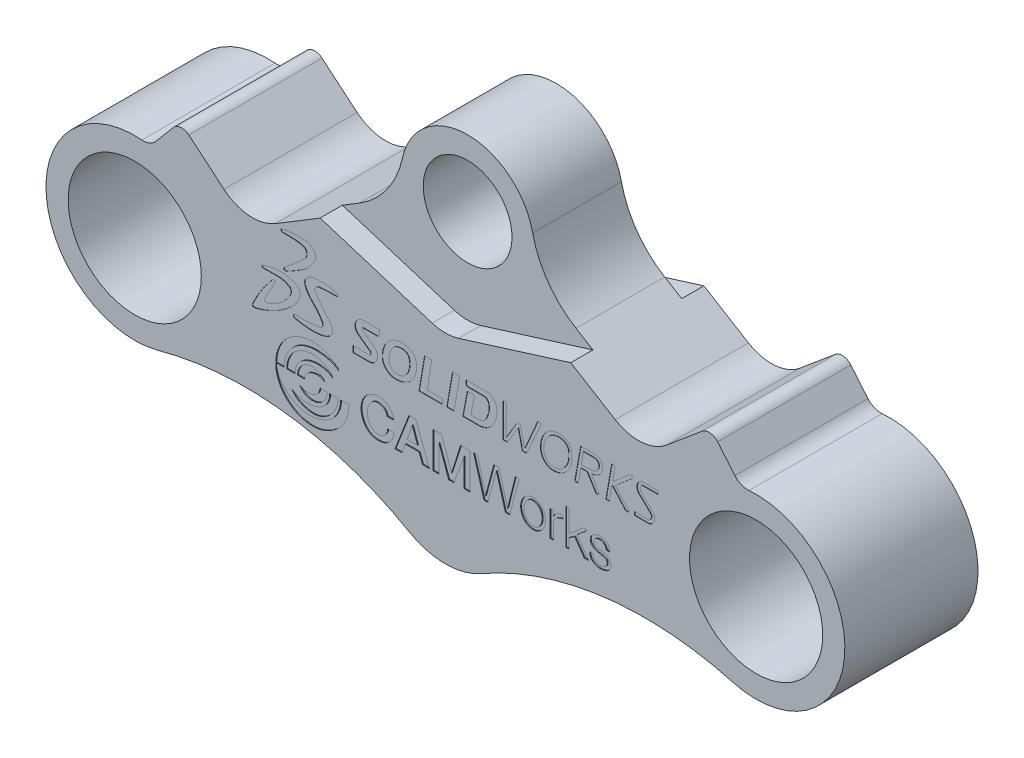
SolidWorks part; units mm, degrees
material "6061-T6 (SS)"
ref_plane "Front Plane" through (0, 0, 0) normal (0, 0, 1) x (1, 0, 0)
ref_plane "Top Plane" through (0, 0, 0) normal (0, 1, 0) x (1, 0, 0)
ref_plane "Right Plane" through (0, 0, 0) normal (1, 0, 0) x (0, 0, -1)
sketch "Sketch1" plane through (0, 0, 0) normal (0, 0, 1) x (1, 0, 0)
  line L0 (0, 0) -> (44.45, 7.8377) construction
  line L1 (0, 0) -> (0, 31.75) construction
  line L2 (0, 0) -> (0, -25.1431) construction
  line L3 (0, 0) -> (113.4618, 0) construction
  line L4 (44.45, 7.8377) -> (33.8059, 20.5229) construction
  line L5 (44.45, 7.8377) -> (44.45, 35.5738) construction
  line L11 (37.9229, 25.4953) -> (41.4081, 21.3418)
  line L13 (37.9229, 25.4953) -> (28.1941, 17.3319)
  line L14 (-44.45, 7.8377) -> (-33.8059, 20.5229) construction
  line L17 (28.1941, 17.3319) -> (15.505, 25.046)
  line L18 (0, 0) -> (-44.45, 7.8377) construction
  line L19 (-28.1941, 17.3319) -> (-15.505, 25.046)
  line L22 (-37.9229, 25.4953) -> (-28.1941, 17.3319)
  line L24 (-37.9229, 25.4953) -> (-41.4081, 21.3418)
  circle A0 centre (0, 31.75) radius 7.9375 construction
  circle A2 centre (0, 0) radius 5.5562 construction
  circle A3 centre (44.45, 7.8377) radius 9.525 construction
  arc A5 (41.4081, 21.3418) -> (43.429, 20.4966) centre (43.2371, 22.8765) ccw
  circle A7 centre (0, 31.75) radius 9.525 construction
  arc A8 (10.3187, 0) -> (10.162, 1.7918) centre (0, 0) ccw
  arc A9 (5.1295, -8.9535) -> (41.0791, -4.4067) centre (28.5656, -49.8611) cw
  arc A10 (9.3119, 33.7533) -> (-9.3119, 33.7533) centre (0, 31.75) ccw
  arc A11 (15.505, 25.046) -> (9.3119, 33.7533) centre (22.5268, 36.5963) cw
  arc A12 (41.0791, -4.4067) -> (43.429, 20.4966) centre (44.45, 7.8377) ccw
  circle A13 centre (0, 0) radius 10.3187 construction
  arc A14 (-41.0791, -4.4067) -> (-43.429, 20.4966) centre (-44.45, 7.8377) cw
  arc A15 (-15.505, 25.046) -> (-9.3119, 33.7533) centre (-22.5268, 36.5963) ccw
  arc A16 (-5.1295, -8.9535) -> (-41.0791, -4.4067) centre (-28.5656, -49.8611) ccw
  arc A19 (-41.4081, 21.3418) -> (-43.429, 20.4966) centre (-43.2371, 22.8765) cw
  circle A21 centre (-44.45, 7.8377) radius 9.525 construction
  arc A22 (-5.1295, -8.9535) -> (5.1295, -8.9535) centre (0, 0) ccw
  point P26 (9.1088, 28.1848)
  point P35 (9.8679, 3.0169)
  dimension "D1" = 15.875
  dimension "D3" = 11.1125
  dimension "D6" = 19.05
  dimension "D12" = 2.3876
  dimension "D4" = 44.45
  dimension "D5" = 31.75
  dimension "D7" = 10
  dimension "D8" = 40
  dimension "D16" = 4.7625
  dimension "D17" = 1.5875
extrude "Boss-Extrude1" add sketch "Sketch1" along normal mid plane 19.05 contours A16 A22 A9 A12 A5 L11 A3 L13 L17 A11 A10 A15 L19 L22 A21 L24 A19 A14 A0 A2 region at (0, 10.8738, 0)
fillet "Fillet19" radius 6.35 2 edges at (28.1941, 17.3319, 0) (-28.1941, 17.3319, 0)
fillet "Fillet20" radius 1.5875 2 edges at (37.9229, 25.4953, 0) (-37.9229, 25.4953, 0)
sketch "Sketch2" plane through (0, 0, 9.525) normal (0, 0, 1) x (1, 0, 0)
  line L0 (11.5116, 28.7617) -> (22.65, -3.0883)
  line L1 (22.65, -3.0883) -> (47.5098, -15.7051)
  line L2 (47.5098, -15.7051) -> (71.0787, 26.7896)
  line L3 (71.0787, 26.7896) -> (23.8861, 37.9468)
  line L4 (23.8861, 37.9468) -> (11.5116, 28.7617)
  arc A0 (9.3119, 33.7533) -> (15.505, 25.046) centre (22.5268, 36.5963) ccw construction
  arc A1 (41.0791, -4.4067) -> (5.1295, -8.9535) centre (28.5656, -49.8611) ccw construction
sketch "Sketch3" plane through (0, 0, 9.525) normal (0, 0, 1) x (1, 0, 0)
  line L0 (0, 0) -> (0, 51.1761) construction
  line L1 (-13.039, 44.2465) -> (13.039, 44.2465)
  line L2 (13.039, 44.2465) -> (19.3473, 24.0178)
  line L3 (19.3473, 24.0178) -> (0, 17.9843)
  line L4 (-19.3473, 24.0178) -> (0, 17.9843)
  line L5 (-13.039, 44.2465) -> (-19.3473, 24.0178)
  point P9 (0, 44.2465)
extrude "Cut-Extrude2" cut sketch "Sketch3" against normal blind 3.175
fillet "Fillet9" radius 6.35 1 edges at (0, 17.9843, 7.9375)
mirror "Mirror13" about plane through (0, 0, 0) normal (0, 0, 1) of "Cut-Extrude2"
fillet "Fillet14" radius 6.35 1 edges at (0, 17.9843, -7.9375)
hole_wizard "1/2 (0.5) Diameter Hole1" positions "Sketch11" profile "Sketch12" hole size "1/2" standard "ANSI Inch" end condition through all
sketch "Sketch11" plane through (0, 0, 6.35) normal (0, 0, 1) x (1, 0, 0)
  point P0 (0, 31.75)
sketch "Sketch12" plane through (0, 31.75, 6.35) normal (1, 0, 0) x (0, -1, 0)
  line L0 (0, 0) -> (0, 15.875)
  line L1 (0, 15.875) -> (6.35, 15.875)
  line L2 (6.35, 15.875) -> (6.35, 0)
  line L5 (6.35, 0) -> (0, 0)
  line L11 (0, -6.35) -> (0, 107.95) construction
  dimension "Thru Hole Dia." = 12.7
  dimension "Thru Hole Depth" = 15.875
hole_wizard "3/4 (0.75) Diameter Hole1" positions "Sketch13" profile "Sketch14" hole size "3/4" standard "ANSI Inch" end condition through all
sketch "Sketch13" plane through (0, 0, 9.525) normal (0, 0, 1) x (1, 0, 0)
  point P0 (-44.45, 7.8377)
  point P3 (44.45, 7.8377)
sketch "Sketch14" plane through (-44.45, 7.8377, 9.525) normal (1, 0, 0) x (0, -1, 0)
  line L0 (0, 0) -> (0, 19.05)
  line L1 (0, 19.05) -> (9.525, 19.05)
  line L2 (9.525, 19.05) -> (9.525, 0)
  line L5 (9.525, 0) -> (0, 0)
  line L11 (0, -6.35) -> (0, 107.95) construction
  dimension "Thru Hole Dia." = 19.05
  dimension "Thru Hole Depth" = 19.05
sketch "Sketch19" plane through (0, 0, 9.525) normal (0, 0, 1) x (1, 0, 0)
  line L0 (0, 0) -> (0, 52.7084) construction
  circle A0 centre (44.45, 7.8377) radius 11.1125
  circle A1 centre (-44.45, 7.8377) radius 11.1125
  dimension "D1" = 22.225
sketch "Sketch20" plane through (0, 0, 9.525) normal (0, 0, 1) x (1, 0, 0)
  line L0 (-24.2613, 2.5064) -> (-23.1024, 2.5064)
  line L1 (-21.1371, 2.5064) -> (-20.1303, 2.5064)
  line L2 (-22.6988, 2.5064) -> (-21.5016, 2.5064)
  line L3 (-16.9282, 2.5064) -> (-17.96, 2.5064)
  line L4 (-15.4082, 2.5064) -> (-16.5618, 2.5064)
  line L5 (16.8161, 3.6153) -> (16.8161, 4.1275)
  line L6 (15.4419, 0.3486) -> (15.4419, 2.6934)
  line L7 (14.9756, 0.3486) -> (15.4419, 0.3486)
  line L8 (14.9756, 4.0314) -> (14.9756, 0.3486)
  line L9 (15.4419, 4.0314) -> (14.9756, 4.0314)
  line L10 (15.4419, 3.3134) -> (15.4419, 4.0314)
  line L11 (23.0367, 2.9061) -> (23.4912, 2.9061)
  line L12 (21.1196, 1.5282) -> (20.6711, 1.5282)
  line L24 (-8.3465, 3.7921) -> (-7.4097, 3.7921)
  line L25 (-7.3744, 2.2787) -> (-8.2537, 2.2787)
  line L26 (2.6811, 4.3434) -> (2.6811, 0.3486)
  line L27 (2.6811, 0.3486) -> (3.4934, 0.3486)
  line L28 (3.4934, 0.3486) -> (3.4934, 5.4578)
  line L29 (3.4934, 5.4578) -> (2.1789, 5.4578)
  line L30 (2.1789, 5.4578) -> (0.8894, 1.4078)
  line L31 (0.8894, 1.4078) -> (-0.5714, 5.461)
  line L32 (-0.5714, 5.461) -> (-1.7638, 5.461)
  line L33 (-1.7638, 5.461) -> (-1.7638, 0.3486)
  line L34 (-1.7638, 0.3486) -> (-0.9199, 0.3486)
  line L35 (-0.9199, 0.3486) -> (-0.9199, 4.2121)
  line L36 (-0.9199, 4.2121) -> (0.4726, 0.3486)
  line L37 (0.4726, 0.3486) -> (1.2108, 0.3486)
  line L38 (1.2108, 0.3486) -> (2.6811, 4.3434)
  line L39 (-4.7419, 4.5102) -> (-5.4681, 2.3913)
  line L40 (-3.9888, 2.3913) -> (-4.7419, 4.5102)
  line L41 (-5.4681, 2.3913) -> (-3.9888, 2.3913)
  line L42 (-24.2066, 2.489) -> (-24.2618, 2.489)
  line L43 (-13.8028, 2.5064) -> (-14.9977, 2.5064)
  line L44 (-5.7285, 1.6607) -> (-3.7553, 1.6607)
  line L45 (-6.2391, 0.3486) -> (-5.7285, 1.6607)
  line L46 (-7.2018, 0.3486) -> (-6.2391, 0.3486)
  line L47 (-5.212, 5.461) -> (-7.2018, 0.3486)
  line L48 (-4.2247, 5.461) -> (-5.212, 5.461)
  line L49 (-2.2957, 0.3486) -> (-4.2247, 5.461)
  line L50 (-3.2602, 0.3486) -> (-2.2957, 0.3486)
  line L51 (-3.7553, 1.6607) -> (-3.2602, 0.3486)
  line L52 (17.2152, 0.3486) -> (17.6916, 0.3486)
  line L53 (17.6916, 0.3486) -> (17.6916, 1.7618)
  line L54 (17.6916, 1.7618) -> (18.4695, 2.3165)
  line L55 (18.4695, 2.3165) -> (19.8729, 0.3486)
  line L56 (19.8729, 0.3486) -> (20.4853, 0.3486)
  line L57 (20.4853, 0.3486) -> (18.8132, 2.6934)
  line L58 (18.8132, 2.6934) -> (20.3356, 4.0074)
  line L59 (20.3356, 4.0074) -> (19.7018, 4.0074)
  line L60 (19.7018, 4.0074) -> (17.6916, 2.2723)
  line L61 (17.6916, 2.2723) -> (17.6916, 5.461)
  line L62 (17.6916, 5.461) -> (17.2152, 5.461)
  line L63 (17.2152, 5.461) -> (17.2152, 0.3486)
  line L64 (4.0328, 5.4578) -> (5.522, 0.3486)
  line L65 (5.522, 0.3486) -> (6.0506, 0.3486)
  line L66 (6.0506, 0.3486) -> (7.2887, 4.8318)
  line L67 (7.2887, 4.8318) -> (8.5954, 0.3486)
  line L68 (8.5954, 0.3486) -> (9.1816, 0.3486)
  line L69 (9.1816, 0.3486) -> (10.5463, 5.461)
  line L70 (10.5463, 5.461) -> (10.0007, 5.461)
  line L71 (10.0007, 5.461) -> (8.8885, 0.9778)
  line L72 (8.8885, 0.9778) -> (7.6674, 5.461)
  line L73 (7.6674, 5.461) -> (6.934, 5.461)
  line L74 (6.934, 5.461) -> (5.7373, 0.9778)
  line L75 (5.7373, 0.9778) -> (4.6136, 5.4578)
  line L76 (4.6136, 5.4578) -> (4.0328, 5.4578)
  ellipse E0 centre (12.5441, 2.204) end of major axis (12.4598, 0.1977) minor radius 1.779
  ellipse E1 centre (12.5441, 2.204) end of major axis (12.5441, 3.7921) minor radius 1.3127
  spline S0 degree 3 poles (-23.1024, 2.5064) (-23.0971, 3.5859) (-22.4651, 5.2251) (-20.5491, 6.6301) (-18.078, 7.1112) (-16.1966, 6.6039) (-15.1548, 5.9628) knots 0 0 0 0 0.304367 0.466255 0.655371 1 1 1 1
  spline S1 degree 3 poles (-15.1548, 5.9628) (-15.5783, 6.5498) (-16.8375, 7.4484) (-18.9616, 7.893) (-21.0692, 7.4482) (-23.4121, 5.9658) (-24.2655, 3.8586) (-24.2613, 2.5064) knots 0 0 0 0 0.172137 0.357725 0.501203 0.677746 1 1 1 1
  spline S2 degree 3 poles (-20.1303, 2.5064) (-20.1324, 2.9593) (-19.6326, 3.6975) (-18.3871, 4.0366) (-17.5768, 3.8704) (-17.2458, 3.5736) knots 0 0 0 0 0.355167 0.653312 1 1 1 1
  spline S3 degree 3 poles (-17.2458, 3.5736) (-17.4055, 3.9058) (-17.9769, 4.444) (-19.1021, 4.7031) (-20.5335, 4.2616) (-21.1665, 3.2292) (-21.1371, 2.5064) knots 0 0 0 0 0.202687 0.415279 0.607942 1 1 1 1
  spline S4 degree 3 poles (-21.5016, 2.5064) (-21.5879, 3.3398) (-20.8524, 4.5882) (-19.1216, 5.3) (-17.5419, 5.3116) (-16.5539, 4.9658) (-16.1028, 4.6737) knots 0 0 0 0 0.336822 0.562344 0.770945 1 1 1 1
  spline S5 degree 3 poles (-16.1028, 4.6737) (-16.6594, 5.4446) (-18.0791, 6.3254) (-20.166, 6.0885) (-22.0368, 5.0527) (-22.7154, 3.5249) (-22.6988, 2.5064) knots 0 0 0 0 0.313136 0.502366 0.666444 1 1 1 1
  spline S6 degree 3 poles (-17.96, 2.5064) (-17.932, 1.8223) (-19.0083, 0.9185) (-20.3256, 1.0433) (-20.8296, 1.4355) knots 0 0 0 0 0.499578 1 1 1 1
  spline S7 degree 3 poles (-20.8296, 1.4355) (-20.5724, 0.9811) (-19.817, 0.3947) (-18.5061, 0.3779) (-17.3016, 1.0011) (-16.9361, 1.9615) (-16.9282, 2.5064) knots 0 0 0 0 0.287736 0.487574 0.695315 1 1 1 1
  spline S8 degree 3 poles (-16.5618, 2.5064) (-16.5115, 1.8371) (-16.9702, 0.6799) (-18.4014, -0.1179) (-20.0813, -0.4016) (-21.3098, -0.08) (-21.9604, 0.3429) knots 0 0 0 0 0.283056 0.482539 0.671248 1 1 1 1
  spline S9 degree 3 poles (-21.9604, 0.3429) (-21.5349, -0.3362) (-20.3963, -1.0126) (-18.5359, -1.271) (-16.9531, -0.6568) (-15.733, 0.6766) (-15.316, 1.8629) (-15.4082, 2.5064) knots 0 0 0 0 0.257455 0.416875 0.60526 0.789878 1 1 1 1
  spline S10 degree 3 poles (15.4419, 2.6934) (15.602, 2.9028) (15.8927, 3.463) (16.5054, 3.6094) (16.8161, 3.6153) knots 0 0 0 0 0.469307 1 1 1 1
  spline S11 degree 3 poles (16.8161, 4.1275) (16.2755, 4.1602) (15.6912, 3.8377) (15.4419, 3.3134) knots 0 0 0 0 1 1 1 1
  spline S12 degree 3 poles (23.4912, 2.9061) (23.5069, 3.3021) (23.4377, 3.5745) (22.8174, 4.1301) (22.0633, 4.2006) (21.4391, 4.1124) (20.7962, 3.6676) (20.6048, 2.8681) (21.4202, 2.0292) (22.2991, 2.0194) (23.1045, 1.7199) (23.2793, 1.0222) (22.5578, 0.5504) (21.6195, 0.5811) (21.0009, 1.1205) (21.1196, 1.5282) knots 0 0 0 0 0.067062 0.148975 0.20304 0.28682 0.328691 0.4252 0.488568 0.640215 0.674333 0.728187 0.813903 0.886703 1 1 1 1
  spline S13 degree 3 poles (20.6711, 1.5282) (20.614, 1.2217) (20.7979, 0.6477) (21.6707, 0.1651) (22.6282, 0.1318) (23.6557, 0.6248) (23.8047, 1.6699) (23.0039, 2.4509) (22.1415, 2.4551) (21.281, 2.7015) (21.2066, 3.5303) (21.8459, 3.7244) (22.6106, 3.789) (23.0273, 3.129) (23.0367, 2.9061) knots 0 0 0 0 0.091071 0.156874 0.280395 0.364886 0.466496 0.536468 0.665479 0.716573 0.778128 0.84612 0.890812 1 1 1 1
  spline S14 degree 3 poles (-7.4097, 3.7921) (-7.4612, 4.6654) (-8.603, 5.7637) (-10.3346, 5.5952) (-11.6171, 4.8127) (-12.1965, 3.3447) (-11.9341, 1.6356) (-11.0709, 0.4637) (-9.6771, 0.0852) (-8.2935, 0.3052) (-7.4939, 1.3895) (-7.3516, 2.0564) (-7.3744, 2.2787) knots 0 0 0 0 0.175331 0.271237 0.33858 0.47311 0.570736 0.688741 0.747217 0.858562 0.957457 1 1 1 1
  spline S15 degree 3 poles (-8.2537, 2.2787) (-8.2617, 1.7264) (-8.8948, 0.8033) (-10.1462, 0.9543) (-10.8222, 1.5142) (-11.2318, 2.5289) (-11.1606, 3.8265) (-10.1272, 4.9836) (-8.7838, 4.7625) (-8.3631, 4.0824) (-8.3465, 3.7921) knots 0 0 0 0 0.179682 0.286073 0.363963 0.452172 0.627882 0.757863 0.910918 1 1 1 1
  spline S16 degree 3 poles (-14.9977, 2.5064) (-14.9865, 1.5454) (-15.7297, -0.601) (-18.5104, -1.765) (-21.465, -1.4226) (-23.6002, 0.1837) (-24.1678, 1.9265) (-24.2066, 2.489) knots 0.001261 0.001261 0.001261 0.001261 0.216474 0.470316 0.597834 0.876936 1 1 1 1
  spline S17 degree 3 poles (-24.2618, 2.489) (-24.2696, 2.2031) (-24.2186, 1.4078) (-23.8399, 0.2067) (-22.8245, -1.2742) (-20.9046, -2.6451) (-18.1716, -2.9286) (-16.0515, -1.8894) (-14.3277, -0.2242) (-13.7779, 1.416) (-13.8028, 2.5064) knots 0 0 0 0 0.052567 0.145511 0.227179 0.378978 0.564372 0.699238 0.800017 0.99894 0.99894 0.99894 0.99894
extrude "Cut-Extrude7" cut sketch "Sketch20" against normal blind 0.127 contours L42 S17 L43 S16 | S8 S9 L4 | S6 S7 L3 | S2 S3 L1 | S4 S5 L2 | S0 S1 L0 | L25 S15 L24 S14 | L44 L51 L50 L49 L48 L47 L46 L45 L41 L39 L40 | L75 L76 L64 L65 L66 L67 L68 L69 L70 L71 L72 L73 L74 | E0 E1 | L5 S11 L10 L9 L8 L7 L6 S10 | L62 L63 L52 L53 L54 L55 L56 L57 L58 L59 L60 L61 | L12 S13 L11 S12 | L35 L36 L37 L38 L26 L27 L28 L29 L30 L31 L32 L33 L34 region at (-20.848, 7.292, 9.525) region at (-19.6828, 3.707, 9.525) region at (-20.3183, 4.7343, 9.525) region at (-18.3829, 1.3043, 9.525) region at (-17.9104, -0.9069, 9.525) region at (15.9644, 3.4053, 9.525) region at (22.1946, 2.1781, 9.525) region at (-11.2259, 2.7056, 9.525) region at (-19.4824, -1.7214, 9.525) region at (-6.0498, 1.0303, 9.525) region at (18.3267, 2.5398, 9.525) region at (4.3232, 5.375, 9.525) region at (12.6262, 4.1567, 9.525)
sketch "Sketch22" plane through (0, 0, 9.525) normal (0, 0, 1) x (1, 0, 0)
  line L0 (128.642, -102.015) -> (744.642, -102.015) construction
  line L1 (-2.9817, 13.981) -> (-3.772, 9.2249)
  line L2 (-3.772, 9.2249) -> (-0.4945, 9.2249)
  line L3 (-0.4945, 9.2249) -> (-0.3768, 9.9328)
  line L4 (-0.3768, 9.9328) -> (-2.6267, 9.9328)
  line L5 (-2.6267, 9.9328) -> (-1.954, 13.981)
  line L6 (-1.954, 13.981) -> (-2.9817, 13.981)
  line L7 (1.0211, 13.981) -> (2.0499, 13.981)
  line L8 (2.0499, 13.981) -> (1.2305, 9.2249)
  line L9 (1.2305, 9.2249) -> (0.2017, 9.2249)
  line L10 (0.2017, 9.2249) -> (1.0211, 13.981)
  line L11 (3.1314, 12.6346) -> (4.1476, 12.6346)
  line L12 (4.1476, 12.6346) -> (3.6475, 9.9687)
  line L13 (3.6475, 9.9687) -> (4.831, 9.9687)
  line L14 (-9.4112, 13.981) -> (-11.7339, 13.981)
  line L15 (-13.1933, 10.13) -> (-10.9089, 10.13)
  line L16 (-13.1933, 10.13) -> (-13.1933, 9.2599)
  line L17 (-13.1933, 9.2599) -> (-10.9525, 9.2599)
  line L18 (-12.4337, 11.8297) -> (-10.788, 10.6322)
  line L19 (-10.2413, 11.5241) -> (-11.8393, 12.6869)
  line L20 (-11.7836, 13.0429) -> (-9.652, 13.0429)
  line L21 (-9.652, 13.0429) -> (-9.4112, 13.3557)
  line L22 (-9.4112, 13.3557) -> (-9.4112, 13.981)
  line L23 (3.1314, 12.6346) -> (2.4906, 9.2182)
  line L24 (2.4906, 9.2182) -> (4.7833, 9.2182)
  line L25 (5.7029, 13.981) -> (2.9784, 13.981)
  line L26 (3.2614, 13.2046) -> (5.5148, 13.2046)
  line L27 (8.2456, 13.981) -> (8.2456, 9.1881)
  line L28 (8.2456, 9.1881) -> (8.8753, 9.1881)
  line L29 (8.8753, 9.1881) -> (10.4222, 11.7688)
  line L30 (10.4222, 11.7688) -> (10.9975, 9.1881)
  line L31 (10.9975, 9.1881) -> (11.6038, 9.1881)
  line L32 (11.6038, 9.1881) -> (13.7013, 13.7935)
  line L33 (13.7013, 13.7935) -> (13.6595, 13.981)
  line L34 (13.6595, 13.981) -> (13.2328, 13.981)
  line L35 (13.2328, 13.981) -> (11.3894, 9.7227)
  line L36 (11.3894, 9.7227) -> (11.3007, 9.7227)
  line L37 (11.3007, 9.7227) -> (10.7305, 12.2808)
  line L38 (10.7305, 12.2808) -> (10.245, 12.2808)
  line L39 (10.245, 12.2808) -> (8.7639, 9.81)
  line L40 (8.7639, 9.81) -> (8.6704, 9.81)
  line L41 (8.6704, 9.81) -> (8.7172, 13.981)
  line L42 (8.7172, 13.981) -> (8.2456, 13.981)
  line L43 (19.3559, 13.9497) -> (18.4979, 9.1881)
  line L44 (18.4979, 9.1881) -> (19.0009, 9.1881)
  line L45 (19.0009, 9.1881) -> (19.3711, 11.2425)
  line L46 (19.3711, 11.2425) -> (20.2877, 11.2425)
  line L47 (20.2877, 11.2425) -> (21.5443, 9.1881)
  line L48 (21.5443, 9.1881) -> (21.8765, 9.1881)
  line L49 (21.8765, 9.1881) -> (21.9714, 9.2599)
  line L50 (21.9714, 9.2599) -> (21.9714, 9.4455)
  line L51 (21.9714, 9.4455) -> (20.9322, 11.1444)
  line L52 (19.3559, 13.9497) -> (21.493, 13.9497)
  line L53 (20.9322, 11.2816) -> (20.9322, 11.1444)
  line L54 (19.7193, 13.4693) -> (19.455, 11.7225)
  line L55 (19.455, 11.7225) -> (20.3274, 11.7225)
  line L56 (19.7193, 13.4693) -> (21.3007, 13.4693)
  line L57 (23.7899, 13.9497) -> (22.9678, 9.1881)
  line L58 (22.9678, 9.1881) -> (23.4569, 9.1881)
  line L59 (23.4569, 9.1881) -> (23.8184, 11.2816)
  line L60 (23.8184, 11.2816) -> (23.946, 11.2816)
  line L61 (23.946, 11.2816) -> (25.767, 9.1881)
  line L62 (25.767, 9.1881) -> (26.1625, 9.1881)
  line L63 (26.1625, 9.1881) -> (26.2605, 9.3813)
  line L64 (26.2605, 9.3813) -> (24.2974, 11.5266)
  line L65 (24.2974, 11.5266) -> (26.8031, 13.7009)
  line L66 (26.8031, 13.7009) -> (26.8031, 13.9497)
  line L67 (26.8031, 13.9497) -> (26.3865, 13.9497)
  line L68 (26.3865, 13.9497) -> (23.946, 11.832)
  line L69 (23.946, 11.832) -> (24.2344, 13.8253)
  line L70 (24.2344, 13.8253) -> (24.1265, 13.9497)
  line L71 (24.1265, 13.9497) -> (23.7899, 13.9497)
  line L72 (30.4315, 13.9497) -> (28.1771, 13.9497)
  line L73 (27.7505, 12.1488) -> (29.2938, 10.682)
  line L74 (28.9432, 9.6786) -> (27.0483, 9.6964)
  line L75 (30.4315, 13.4925) -> (28.1771, 13.4925)
  line L76 (28.0655, 12.4802) -> (29.6088, 11.0134)
  line L77 (28.9388, 9.2214) -> (27.044, 9.2392)
  line L78 (30.4315, 13.9497) -> (30.4315, 13.4925)
  line L79 (27.0483, 9.6964) -> (27.044, 9.2392)
  line L80 (-23.039, 14.9078) -> (-21.8627, 15.8733)
  line L81 (2.9784, 13.3941) -> (2.9784, 13.981)
  arc A0 (-11.8393, 12.6869) -> (-11.7836, 13.0429) centre (-11.7201, 12.8506) cw
  arc A1 (-11.7339, 13.981) -> (-12.4337, 11.8297) centre (-11.7339, 12.7915) ccw
  arc A2 (-10.788, 10.6322) -> (-10.9089, 10.13) centre (-10.9525, 10.4061) cw
  arc A3 (-10.9525, 9.2599) -> (-10.2413, 11.5241) centre (-10.9525, 10.5037) ccw
  arc A4 (4.7833, 9.2182) -> (6.7117, 10.2158) centre (4.7833, 11.5808) ccw
  arc A5 (6.7117, 10.2158) -> (7.3259, 11.5671) centre (3.4936, 12.4937) ccw
  arc A6 (7.3259, 11.5671) -> (7.1901, 13.1196) centre (4.9502, 12.1415) ccw
  arc A7 (7.1901, 13.1196) -> (6.3859, 13.8651) centre (5.9338, 12.571) ccw
  arc A8 (6.3859, 13.8651) -> (5.7029, 13.981) centre (5.7029, 11.9102) ccw
  arc A9 (5.5148, 13.2046) -> (6.1315, 12.7825) centre (5.5148, 12.5431) cw
  arc A10 (6.1315, 12.7825) -> (6.2047, 11.6047) centre (4.3188, 12.0787) cw
  arc A11 (6.2047, 11.6047) -> (5.8719, 10.6917) centre (1.6368, 12.7527) cw
  arc A12 (4.831, 9.9687) -> (5.8719, 10.6917) centre (4.831, 11.0795) ccw
  arc A13 (-24.7542, 12.5152) -> (-27.6149, 8.0822) centre (-11.0495, 0.5318) ccw
  arc A14 (-27.6149, 8.0822) -> (-27.3909, 7.7836) centre (-27.4214, 7.994) ccw
  arc A15 (-27.3909, 7.7836) -> (-26.4475, 7.994) centre (-28.3136, 14.1415) ccw
  arc A16 (-26.4475, 7.994) -> (-21.8071, 10.7493) centre (-29.7299, 18.8073) ccw
  arc A17 (-21.8071, 10.7493) -> (-20.8263, 12.3784) centre (-24.4815, 13.4693) ccw
  arc A18 (-20.8263, 12.3784) -> (-20.8773, 13.1196) centre (-21.8402, 12.681) ccw
  arc A19 (-20.8773, 13.1196) -> (-21.634, 13.7838) centre (-21.9932, 12.6113) ccw
  arc A20 (-21.634, 13.7838) -> (-22.2572, 13.9543) centre (-24.7753, 3.5301) ccw
  arc A21 (-22.2572, 13.9543) -> (-25.6583, 13.7733) centre (-23.6547, 8.1691) ccw
  arc A22 (-25.6583, 13.7733) -> (-26.1478, 13.5938) centre (-14.8129, -16.5622) ccw
  arc A23 (-26.1478, 13.5938) -> (-26.1547, 13.3557) centre (-26.1025, 13.4734) ccw
  arc A24 (-26.1547, 13.3557) -> (-25.8123, 13.2928) centre (-25.8522, 14.0385) ccw
  arc A25 (-25.8123, 13.2928) -> (-23.6606, 13.2927) centre (-24.7367, -6.81) cw
  arc A26 (-23.6606, 13.2927) -> (-22.6962, 13.0429) centre (-23.7947, 10.7887) cw
  arc A27 (-22.6962, 13.0429) -> (-22.3206, 12.8506) centre (-27.3882, 3.4145) cw
  arc A28 (-22.3206, 12.8506) -> (-22.1349, 12.6238) centre (-22.5021, 12.5127) cw
  arc A29 (-22.1349, 12.6238) -> (-22.2316, 11.8297) centre (-23.0846, 12.3365) cw
  arc A30 (-22.2316, 11.8297) -> (-25.1553, 9.3724) centre (-27.2147, 14.7906) cw
  arc A31 (-25.1553, 9.3724) -> (-25.6483, 9.259) centre (-25.813, 11.1029) cw
  arc A32 (-25.6483, 9.259) -> (-25.8683, 9.5496) centre (-25.6674, 9.4731) cw
  arc A33 (-24.7542, 12.5152) -> (-24.4831, 12.6067) centre (-24.5401, 12.328) cw
  arc A34 (-24.4831, 12.6067) -> (-24.3969, 12.4524) centre (-24.5065, 12.4924) cw
  arc A35 (-24.3969, 12.4524) -> (-25.0673, 11.1029) centre (-30.7594, 14.7718) cw
  arc A36 (-25.0673, 11.1029) -> (-25.8683, 9.5496) centre (-17.4402, 6.1867) ccw
  arc A37 (15.5711, 13.3941) -> (16.8835, 13.3941) centre (16.2273, 11.5266) cw
  arc A38 (15.5711, 13.3941) -> (14.5077, 12.5431) centre (16.254, 11.4508) ccw
  arc A39 (14.5077, 12.5431) -> (14.1532, 11.7225) centre (17.0241, 10.9691) ccw
  arc A40 (14.1532, 11.7225) -> (14.0724, 10.7493) centre (16.8851, 11.0056) ccw
  arc A41 (14.0724, 10.7493) -> (14.5901, 9.7227) centre (15.6306, 10.8913) ccw
  arc A42 (14.5901, 9.7227) -> (15.1733, 9.4455) centre (15.3569, 10.5839) ccw
  arc A43 (15.1733, 9.4455) -> (16.9255, 10.0368) centre (15.4889, 11.4023) ccw
  arc A44 (16.9255, 10.0368) -> (17.2922, 10.5037) centre (14.6392, 12.2098) ccw
  arc A45 (17.2922, 10.5037) -> (17.5668, 11.1512) centre (15.5481, 11.6253) ccw
  arc A46 (17.5668, 11.1512) -> (17.6213, 12.5431) centre (14.0045, 11.9879) ccw
  arc A47 (17.6213, 12.5431) -> (17.3551, 13.0623) centre (16.7088, 12.403) ccw
  arc A48 (17.3551, 13.0623) -> (16.8835, 13.3941) centre (16.1062, 11.7884) ccw
  arc A49 (18.0118, 11.0466) -> (18.0732, 12.6124) centre (14.0045, 11.9879) ccw
  arc A50 (18.0732, 12.6124) -> (17.6751, 13.3888) centre (16.7088, 12.403) ccw
  arc A51 (17.6751, 13.3888) -> (17.0593, 13.8168) centre (16.1062, 11.7884) ccw
  arc A52 (15.4196, 13.8254) -> (17.0593, 13.8168) centre (16.2273, 11.5266) cw
  arc A53 (15.4196, 13.8254) -> (14.1201, 12.7855) centre (16.254, 11.4508) ccw
  arc A54 (14.1201, 12.7855) -> (13.711, 11.8386) centre (17.0241, 10.9691) ccw
  arc A55 (13.711, 11.8386) -> (13.6171, 10.7078) centre (16.8851, 11.0056) ccw
  arc A56 (13.6171, 10.7078) -> (14.2861, 9.3813) centre (15.6306, 10.8913) ccw
  arc A57 (14.2861, 9.3813) -> (15.1005, 8.9942) centre (15.3569, 10.5839) ccw
  arc A58 (15.1005, 8.9942) -> (17.2569, 9.7219) centre (15.4889, 11.4023) ccw
  arc A59 (17.2569, 9.7219) -> (17.6767, 10.2564) centre (14.6392, 12.2098) ccw
  arc A60 (17.6767, 10.2564) -> (18.0118, 11.0466) centre (15.5481, 11.6253) ccw
  arc A61 (21.493, 13.9497) -> (22.4136, 13.2776) centre (21.493, 12.983) cw
  arc A62 (22.4136, 13.2776) -> (21.7715, 11.5724) centre (21.0159, 12.8304) cw
  arc A63 (21.7715, 11.5724) -> (21.5625, 11.4649) centre (20.8526, 13.1024) cw
  arc A64 (21.5625, 11.4649) -> (20.9322, 11.2816) centre (20.5242, 13.8596) cw
  arc A65 (21.3007, 13.4693) -> (21.971, 12.8373) centre (21.3007, 12.7978) cw
  arc A66 (21.971, 12.8373) -> (21.9722, 12.8037) centre (21.2163, 12.7929) cw
  arc A67 (21.9722, 12.8037) -> (21.1243, 11.7884) centre (20.9578, 12.7892) cw
  arc A68 (21.1243, 11.7884) -> (20.3274, 11.7225) centre (20.3274, 16.5787) cw
  arc A69 (28.1771, 13.9497) -> (27.8237, 13.8261) centre (28.1771, 13.3826) ccw
  arc A70 (27.8237, 13.8261) -> (27.7505, 12.1488) centre (28.5173, 12.9556) ccw
  arc A71 (29.2938, 10.682) -> (29.3156, 9.8365) centre (28.8817, 10.2483) cw
  arc A72 (29.3156, 9.8365) -> (28.9432, 9.6786) centre (28.9479, 10.1855) cw
  arc A73 (28.1771, 13.4925) -> (28.1086, 13.4685) centre (28.1771, 13.3826) ccw
  arc A74 (28.1086, 13.4685) -> (28.0655, 12.4802) centre (28.5173, 12.9556) ccw
  arc A75 (29.6088, 11.0134) -> (29.6472, 9.5217) centre (28.8817, 10.2483) cw
  arc A76 (29.6472, 9.5217) -> (28.9388, 9.2214) centre (28.9479, 10.1855) cw
  arc A77 (-21.8627, 15.8733) -> (-20.0559, 17.5348) centre (-35.7156, 32.751) ccw
  arc A78 (-20.0559, 17.5348) -> (-20.1458, 18.7689) centre (-20.6497, 18.1118) ccw
  arc A79 (-20.1458, 18.7689) -> (-20.3126, 18.8549) centre (-20.4685, 18.348) ccw
  arc A80 (-20.3126, 18.8549) -> (-21.5028, 19.0669) centre (-21.7706, 14.1161) ccw
  arc A81 (-21.5028, 19.0669) -> (-23.2893, 19.1069) centre (-23.029, -9.1448) ccw
  arc A82 (-23.2893, 19.1069) -> (-23.3264, 19.1093) centre (-23.2917, 19.3676) cw
  arc A83 (-23.3264, 19.1093) -> (-23.3349, 19.5353) centre (-23.2977, 19.3229) cw
  arc A84 (-23.3349, 19.5353) -> (-22.1083, 19.7211) centre (-18.7653, -6.4934) cw
  arc A85 (-22.1083, 19.7211) -> (-21.4711, 19.7702) centre (-21.2997, 13.3808) cw
  arc A86 (-21.4711, 19.7702) -> (-20.2203, 19.7578) centre (-21.0137, 2.716) cw
  arc A87 (-20.2203, 19.7578) -> (-19.1699, 19.4261) centre (-20.2856, 17.722) cw
  arc A88 (-19.1699, 19.4261) -> (-18.8328, 19.1313) centre (-20.0559, 18.073) cw
  arc A89 (-18.8328, 19.1313) -> (-18.6816, 17.9053) centre (-19.6716, 18.4055) cw
  arc A90 (-18.6816, 17.9053) -> (-20.6807, 15.7438) centre (-23.4606, 20.3201) cw
  arc A91 (-20.6807, 15.7438) -> (-22.6397, 14.6234) centre (-42.8948, 52.3124) cw
  arc A92 (-22.6397, 14.6234) -> (-23.0113, 14.6234) centre (-22.8255, 14.9691) cw
  arc A93 (-23.0113, 14.6234) -> (-23.039, 14.9078) centre (-22.9299, 14.7749) cw
  arc A94 (-15.662, 15.4646) -> (-18.9306, 15.6747) centre (-17.7046, 9.2189) ccw
  arc A95 (-18.9306, 15.6747) -> (-19.9811, 14.998) centre (-18.6199, 14.0385) ccw
  arc A96 (-19.9811, 14.998) -> (-20.0792, 14.1739) centre (-19.2678, 14.4952) ccw
  arc A97 (-20.0792, 14.1739) -> (-18.9547, 12.5127) centre (-15.7672, 15.8816) ccw
  arc A98 (-18.9547, 12.5127) -> (-17.6241, 10.8511) centre (-24.2789, 6.8855) cw
  arc A99 (-17.6241, 10.8511) -> (-17.6241, 10.2756) centre (-18.1069, 10.5634) cw
  arc A100 (-17.6241, 10.2756) -> (-18.0533, 9.9972) centre (-18.1211, 10.5719) cw
  arc A101 (-18.0533, 9.9972) -> (-21.5028, 9.8201) centre (-21.1129, 35.9111) cw
  arc A102 (-21.5028, 9.8201) -> (-21.737, 9.4455) centre (-21.5067, 9.5621) ccw
  arc A103 (-21.737, 9.4455) -> (-21.6459, 9.3737) centre (-21.6139, 9.5078) ccw
  arc A104 (-15.662, 15.4646) -> (-15.4208, 15.3316) centre (-15.8914, 14.7632) cw
  arc A105 (-15.4208, 15.3316) -> (-15.4208, 15.1131) centre (-15.5113, 15.2224) cw
  arc A106 (-15.4208, 15.1131) -> (-15.6754, 15.0269) centre (-15.661, 15.4032) cw
  arc A107 (-15.6754, 15.0269) -> (-18.1633, 14.9085) centre (-16.2314, 0.5157) ccw
  arc A108 (-18.1633, 14.9085) -> (-18.6816, 14.5037) centre (-18.0767, 14.2634) ccw
  arc A109 (-18.6816, 14.5037) -> (-18.6199, 14.0385) centre (-18.235, 14.3263) ccw
  arc A110 (-18.6199, 14.0385) -> (-16.4557, 11.2816) centre (41.0474, 58.6485) ccw
  arc A111 (-16.4557, 11.2816) -> (-16.287, 9.9463) centre (-17.4283, 10.4804) cw
  arc A112 (-16.287, 9.9463) -> (-16.6471, 9.5475) centre (-17.1192, 10.3358) cw
  arc A113 (-16.6471, 9.5475) -> (-17.8655, 9.1213) centre (-18.2912, 12.2928) cw
  arc A114 (-17.8655, 9.1213) -> (-20.2885, 9.1213) centre (-19.077, 18.1479) cw
  arc A115 (-20.2885, 9.1213) -> (-21.6459, 9.3737) centre (-18.4662, 22.6987) cw
  arc A116 (3.2614, 13.2046) -> (2.9784, 13.3941) centre (3.2614, 13.5107) cw
  spline S0 degree 3 poles (-5.9536, 13.2322) (-6.5483, 13.2327) (-7.227, 13.0857) (-7.6879, 12.5079) (-7.899, 12.003) (-8.0415, 11.4994) (-8.0515, 11.1444) (-8.0504, 10.8148) (-8.0359, 10.4022) (-7.7211, 9.968) (-7.0997, 9.7294) (-6.3705, 9.6988) (-5.5646, 10.2235) (-5.1198, 11.1786) (-5.0436, 12.1235) (-5.2688, 12.8444) (-5.6179, 13.0798) (-5.9536, 13.2322) (-6.5483, 13.2327) (-7.227, 13.0857) knots -0.106016 -0.074381 -0.037807 0 0.097808 0.150246 0.208882 0.257422 0.302122 0.311658 0.35279 0.422068 0.450225 0.5464 0.621192 0.717548 0.84255 0.893984 0.925619 0.962193 1 1.097808 1.150246 1.208882 only from (-6.3427, 13.2242) to (-6.3427, 13.2242)
  spline S1 degree 3 poles (-5.4548, 13.9527) (-6.5625, 14.0583) (-7.8379, 13.6062) (-8.6566, 12.5996) (-9.0236, 11.513) (-9.1323, 10.1885) (-8.3172, 9.3128) (-7.2611, 8.9285) (-6.1535, 9.0731) (-4.845, 9.7606) (-4.1562, 11.1054) (-4.023, 12.5446) (-4.6287, 13.5603) (-5.4548, 13.9527) (-6.5625, 14.0583) (-7.8379, 13.6062) knots -0.173121 -0.103505 -0.063598 0 0.108437 0.182277 0.243087 0.330527 0.425194 0.446033 0.547798 0.628437 0.724077 0.826879 0.896495 0.936402 1 1.108437 1.182277 1.243087 only from (-6.3272, 13.981) to (-6.3272, 13.981)
extrude "Cut-Extrude9" cut sketch "Sketch22" against normal blind 0.0508
